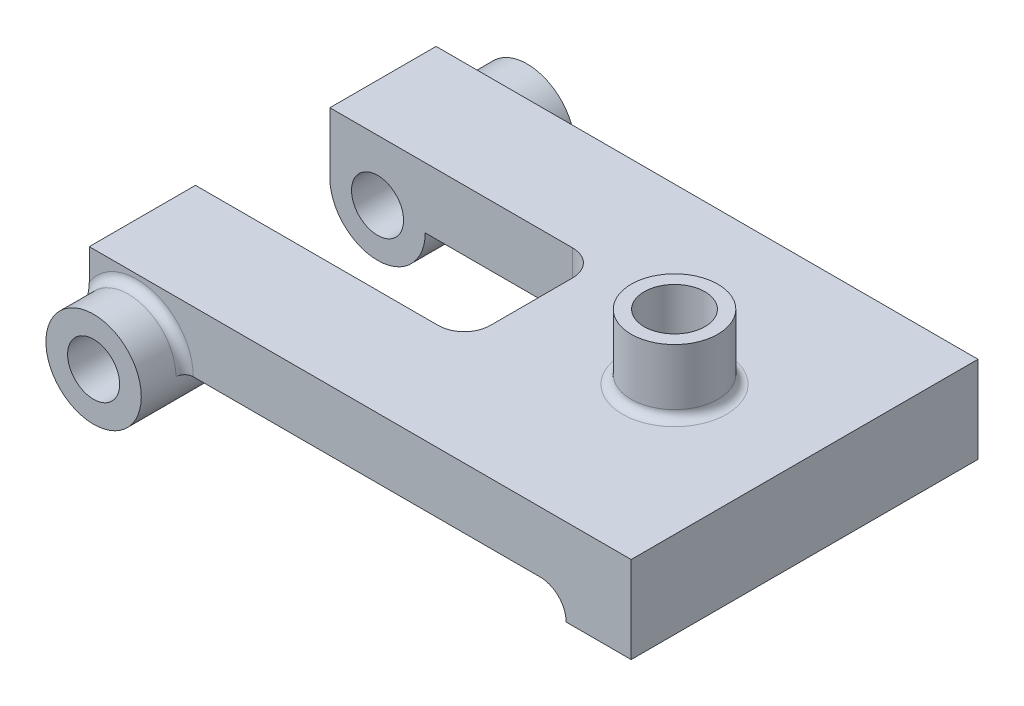
SolidWorks part; units mm, degrees
ref_plane "Front Plane" through (0, 0, 0) normal (0, 0, 1) x (1, 0, 0)
ref_plane "Top Plane" through (0, 0, 0) normal (0, 1, 0) x (1, 0, 0)
ref_plane "Right Plane" through (0, 0, 0) normal (1, 0, 0) x (0, 0, -1)
sketch "Sketch1" plane through (0, 0, 0) normal (0, 0, 1) x (1, 0, 0)
  line L0 (0, 0) -> (0, 14)
  line L1 (0, 14) -> (125, 14)
  line L2 (125, 14) -> (125, -6)
  line L3 (125, -6) -> (110, -6)
  line L4 (104, 0) -> (0, 0)
  arc A0 (110, -6) -> (104, 0) centre (104, -6) ccw
  circle A1 centre (11, 0) radius 11
  circle A2 centre (11, 0) radius 6
  point P12 (117.5, -6)
  point P13 (0, 0)
  point P14 (0, 0)
  point P15 (0, 0)
  dimension "D5" = 22
  dimension "D6" = 12
  dimension "D7" = 6
  dimension "D1" = 125
  dimension "D2" = 110
  dimension "D3" = 6
  dimension "D4" = 20
extrude "Boss-Extrude1" add sketch "Sketch1" along normal mid plane 80 contours A2 L4 A1 | A2 L4 A1 | A1 L4 A0 L3 L2 L1 L0 region at (11, 10.754, 0) region at (71.6062, 6.6855, 0) region at (2.5, -0.246, 0)
extrude "Boss-Extrude2" add sketch "Sketch1<3>" along normal mid plane 100 contours A2 L4 A1 | A2 L4 A1 region at (11, 10.754, 0) region at (2.5, -0.246, 0)
sketch "Sketch1<3>" plane through (0, 0, 0) normal (0, 0, 1) x (1, 0, 0) same geometry as "Sketch1"
sketch "Sketch2" plane through (0, 14, 0) normal (0, 1, 0) x (1, 0, 0)
  line L0 (125, 0) -> (0, 0) construction
  line L1 (125, -40) -> (125, 40) construction
  line L2 (0, -40) -> (0, 40) construction
  line L3 (0, -15.5) -> (62, -15.5)
  line L4 (0, -15.5) -> (0, 15.5)
  line L5 (0, 15.5) -> (62, 15.5)
  line L6 (62, -15.5) -> (62, 15.5)
  dimension "D1" = 31
  dimension "D2" = 62
extrude "Cut-Extrude1" cut sketch "Sketch2" against normal through all
sketch "Sketch3" plane through (0, 14, 0) normal (0, 1, 0) x (1, 0, 0)
  line L0 (125, -40) -> (125, 40) construction
  circle A0 centre (95, 0) radius 10
  circle A2 centre (95, 0) radius 7
  dimension "D1" = 3
  dimension "D2" = 20
  dimension "D3" = 30
extrude "Cut-Extrude2" cut sketch "Sketch3" against normal through all contours A2 region at (95, 14, 0)
extrude "Boss-Extrude3" add sketch "Sketch3<3>" along normal blind 15
sketch "Sketch3<3>" plane through (0, 14, 0) normal (0, 1, 0) x (1, 0, 0) same geometry as "Sketch3"
fillet "Fillet1" radius 6 2 edges at (62, 7, 15.5) (62, 7, -15.5)
fillet "Fillet2" radius 2 3 edges at (95, 14, 10) (11, 11, -40) (11, 11, 40)
